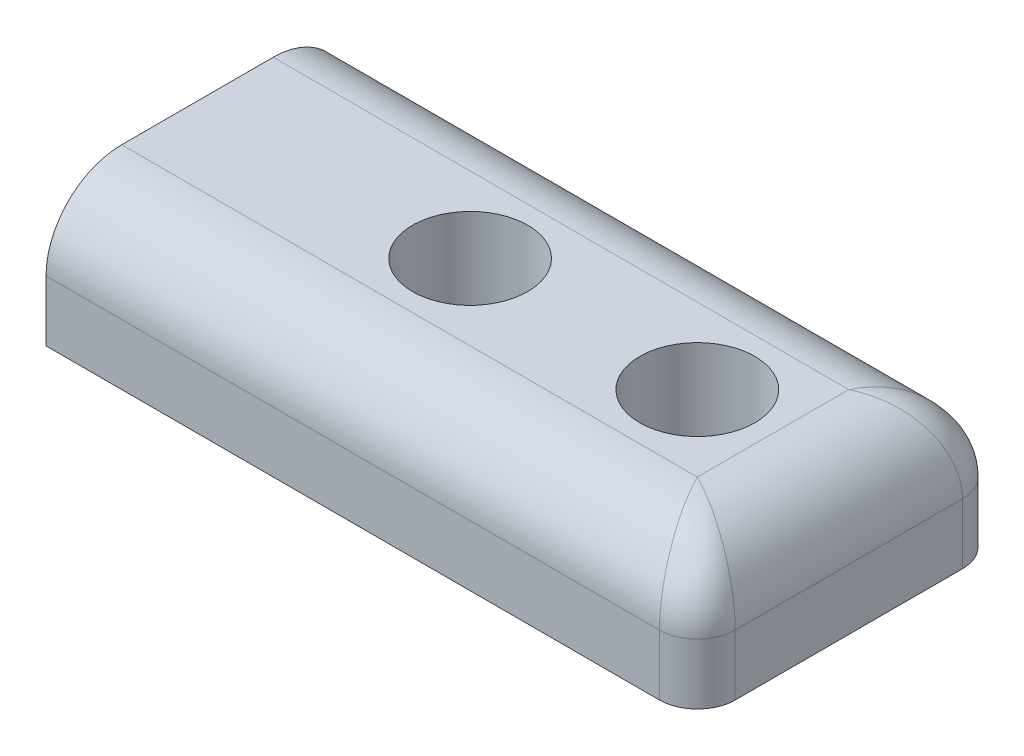
SolidWorks part; units mm, degrees
ref_plane "Front Plane" through (0, 0, 0) normal (0, 0, 1) x (1, 0, 0)
ref_plane "Top Plane" through (0, 0, 0) normal (0, 1, 0) x (1, 0, 0)
ref_plane "Right Plane" through (0, 0, 0) normal (1, 0, 0) x (0, 0, -1)
sketch "Sketch1" plane through (0, 0, 0) normal (0, 1, 0) x (1, 0, 0)
  line L1 (-10.75, 5) -> (10.75, 5)
  line L2 (-10.75, 5) -> (-10.75, -5)
  line L3 (-10.75, -5) -> (10.75, -5)
  line L4 (10.75, 5) -> (10.75, -5)
  line L5 (-10.75, 5) -> (10.75, -5) construction
  line L6 (-10.75, -5) -> (10.75, 5) construction
  point P0 (0, 0)
  dimension "D1" = 21.5
  dimension "D2" = 10
extrude "Boss-Extrude1" add sketch "Sketch1" along normal blind 4.5
sketch "Sketch2" plane through (0, 4.5, 0) normal (0, 1, 0) x (1, 0, 0)
  line L0 (10.75, 0) -> (-1.75, 0)
  line L1 (10.75, -5) -> (10.75, 5) construction
  circle A0 centre (-1.75, 0) radius 1.9
  circle A1 centre (5.75, 0) radius 1.9
  dimension "D2" = 3.8
  dimension "D3" = 3.8
  dimension "D1" = 12.5
  dimension "D4" = 5
extrude "Cut-Extrude1" cut sketch "Sketch2" against normal through all contours A0 | A1
sketch "Sketch5" plane through (-10.75, 0, 0) normal (-1, 0, 0) x (0, 0, 1)
  line L0 (-5, 0) -> (5, 0) construction
  circle A0 centre (0, 0) radius 3.95
  dimension "D1" = 7.9
extrude "Cut-Extrude2" cut sketch "Sketch5" against normal blind 4.1
fillet "Fillet1" radius 2.5 3 edges at (10.75, 4.5, 0) (0, 4.5, -5) (0, 4.5, 5)
fillet "Fillet2" radius 1.25 4 edges at (10.75, 1, -5) (10.75, 1, 5) (10.0178, 3.7678, -4.2678) (10.0178, 3.7678, 4.2678)
